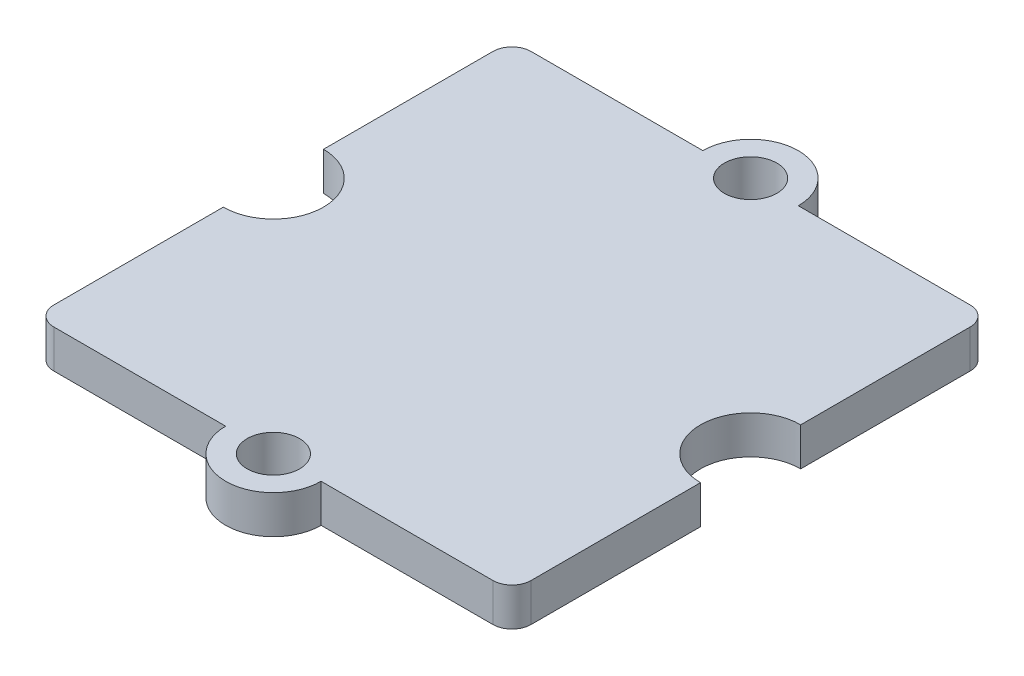
SolidWorks part; units mm, degrees
ref_plane "Plan de face" through (0, 0, 0) normal (0, 0, 1) x (1, 0, 0)
ref_plane "Plan de dessus" through (0, 0, 0) normal (0, 1, 0) x (1, 0, 0)
ref_plane "Plan de droite" through (0, 0, 0) normal (1, 0, 0) x (0, 0, -1)
sketch "Esquisse1" plane through (0, 0, 0) normal (0, 1, 0) x (1, 0, 0)
  line L1 (-9.2, -10) -> (9.2, -10)
  line L2 (-10, -9.2) -> (-10, 9.2)
  line L3 (-9.2, 10) -> (9.2, 10)
  line L4 (10, -9.2) -> (10, 9.2)
  line L5 (-10, -10) -> (10, 10) construction
  line L6 (-10, 10) -> (10, -10) construction
  circle A0 centre (0, 10) radius 2
  circle A1 centre (0, -10) radius 2
  circle A2 centre (-10, 0) radius 2.1
  circle A3 centre (10, 0) radius 2.1
  circle A4 centre (0, 10) radius 1.1
  arc A5 (9.2, 10) -> (10, 9.2) centre (9.2, 9.2) cw
  circle A6 centre (0, -10) radius 1.1
  arc A7 (-9.2, -10) -> (-10, -9.2) centre (-9.2, -9.2) cw
  arc A8 (9.2, -10) -> (10, -9.2) centre (9.2, -9.2) ccw
  arc A9 (-10, 9.2) -> (-9.2, 10) centre (-9.2, 9.2) cw
  point P0 (0, 0)
  dimension "D2" = 0.8
  dimension "D3" = 4.2
  dimension "D4" = 2.2
  dimension "D5" = 4
  dimension "D1" = 20
extrude "Boss.-Extru.1" add sketch "Esquisse1" along normal mid plane 1.6 contours A9 L2 A2 A7 L1 A1 A8 L4 A3 A5 L3 A0 | A4 L3 A0 | A4 L3 A0 | A6 L1 A1 | A6 L1 A1 region at (0, 0, 8.8553) region at (1.55, 0, 10.0447) region at (0, 0, 0) region at (0, 0, -8.0447) region at (1.55, 0, -10.0447)
